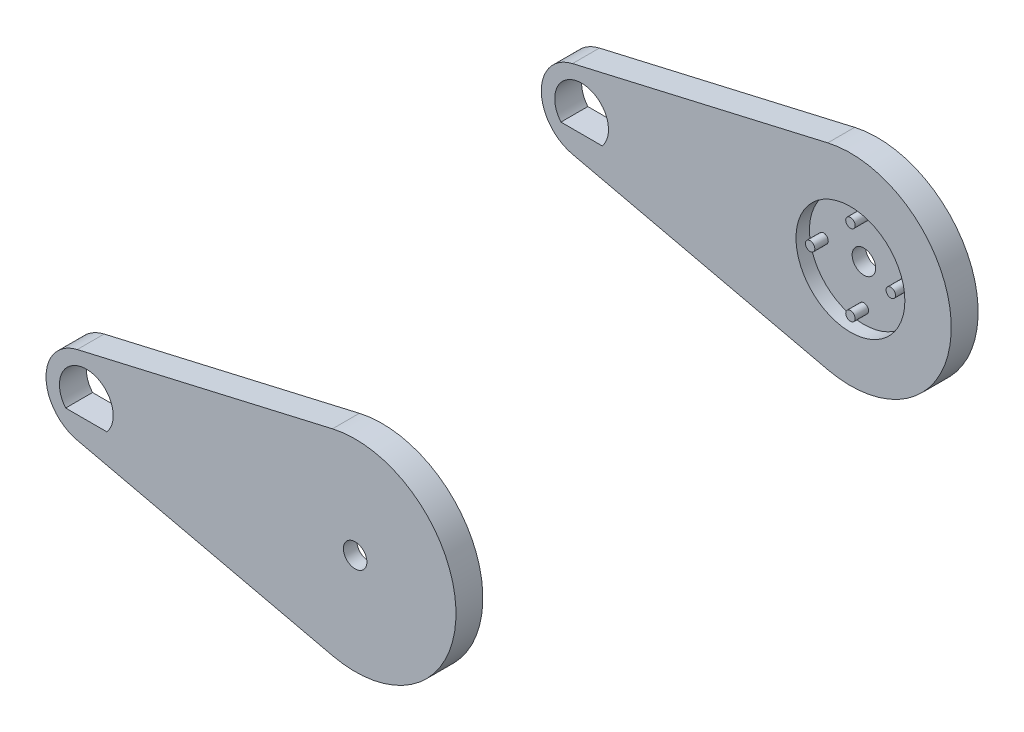
SolidWorks part; units mm, degrees
ref_plane "Front Plane" through (0, 0, 0) normal (0, 0, 1) x (1, 0, 0)
ref_plane "Top Plane" through (0, 0, 0) normal (0, 1, 0) x (1, 0, 0)
ref_plane "Right Plane" through (0, 0, 0) normal (1, 0, 0) x (0, 0, -1)
sketch "Sketch1" plane through (0, 0, 0) normal (0, 0, 1) x (1, 0, 0)
  circle A0 centre (0, 0) radius 15
  circle A10 centre (0, 0) radius 8.1
  circle A11 centre (0, 0) radius 1.75
  point P15 (0, 0)
  point P23 (0, 0)
  dimension "D1" = 30
  dimension "D2" = 16.2
  dimension "D3" = 3.5
extrude "Boss-Extrude1" add sketch "Sketch1" along normal blind 4 contours A0 region at (-14.5757, 0, 0)
extrude "Boss-Extrude2" add sketch "Sketch1<3>" along normal blind 2 contours A10 A11 region at (-7.8709, 0, 0)
sketch "Sketch1<3>" plane through (0, 0, 0) normal (0, 0, 1) x (1, 0, 0) same geometry as "Sketch1"
sketch "Sketch2" plane through (0, 0, 0) normal (0, 0, 1) x (1, 0, 0)
  line L0 (0, 0) -> (-58.5269, 0) construction
  line L1 (-41.35, 5.8462) -> (-3.375, 14.6154)
  line L2 (-41.35, -5.8462) -> (-3.375, -14.6154)
  line L7 (-43.075, -2.5582) -> (-36.925, -2.5582)
  line L8 (-43.075, -2.5582) -> (1.3478, -2.5582) construction
  line L9 (-28.075, -2.5582) -> (-21.925, -2.5582)
  arc A0 (-36.925, -2.5582) -> (-43.075, -2.5582) centre (-40, 0) ccw
  arc A1 (-41.35, 5.8462) -> (-41.35, -5.8462) centre (-40, 0) ccw
  circle A3 centre (0, 0) radius 15 construction
  arc A4 (-21.925, -2.5582) -> (-28.075, -2.5582) centre (-25, 0) ccw
  circle A9 centre (0, 0) radius 15
  arc A10 (-6.925, -2.5582) -> (-13.075, -2.5582) centre (-10, 0) ccw [skipped]
  dimension "D2" = 8
  dimension "D3" = 12
  dimension "D6" = 3
  dimension "D7" = 6.15
  dimension "D1" = 40
extrude "Boss-Extrude3" add sketch "Sketch2" along normal blind 4 contours L1 A1 L2 A4 L9 A0 L7 | L9 A4 region at (-22.2462, 9.7272, 0) region at (-25, 0.4395, 0)
ref_plane "Plane1" through (0, 0, 38.848) normal (0, 0, 1) x (1, 0, 0)
mirror "Mirror2" about plane through (0, 0, 38.848) normal (0, 0, 1) of bodies 103
sketch "Sketch3" plane through (0, 0, 2) normal (0, 0, 1) x (1, 0, 0)
  circle A0 centre (0, 0) radius 6 construction
  circle A1 centre (0, 6) radius 0.7
  circle A2 centre (6, 0) radius 0.7
  circle A3 centre (0, -6) radius 0.7
  circle A4 centre (-6, 0) radius 0.7
  dimension "D1" = 12
  dimension "D2" = 1.4
  dimension "D3" = 1.4
  dimension "D4" = 1.4
  dimension "D5" = 1.4
extrude "Boss-Extrude4" add sketch "Sketch3" along normal up to surface (2 mm away) up to face at (8.1, 0, 4)
